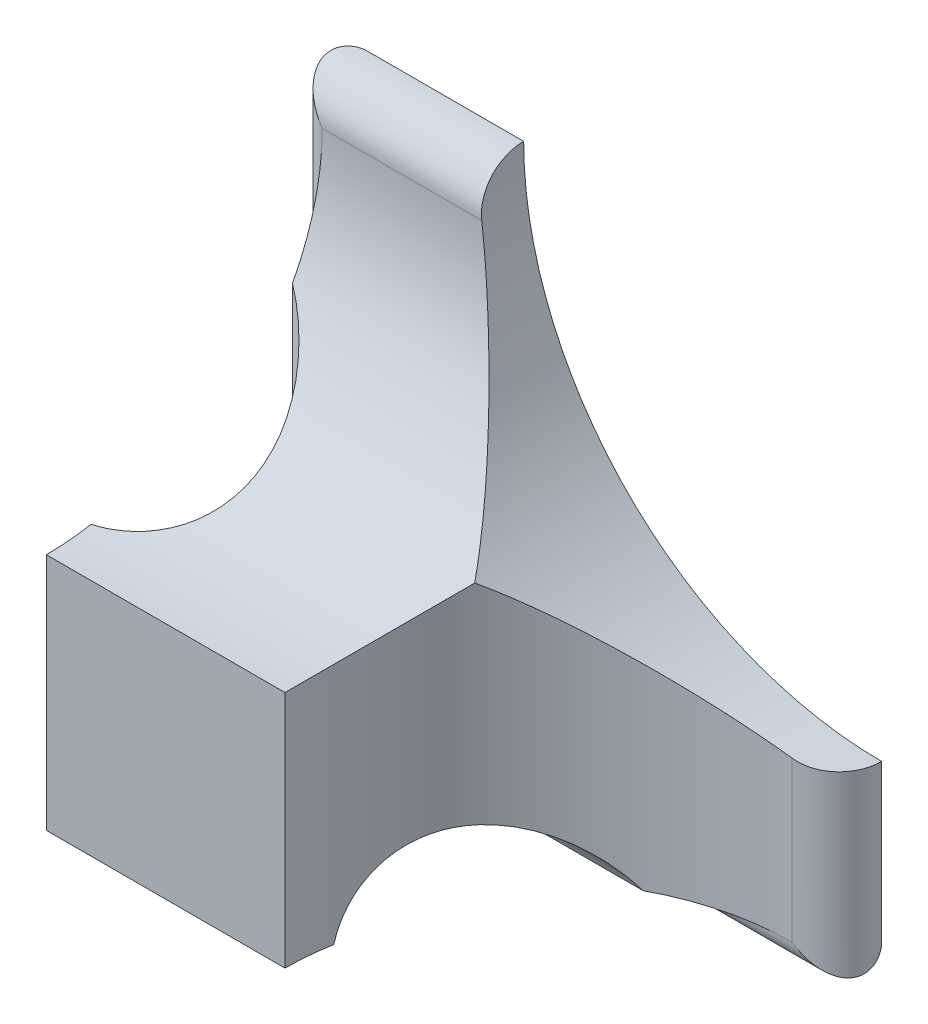
SolidWorks part; units mm, degrees
material "Золото без примесей"
ref_plane "Front" through (0, 0, 0) normal (0, 0, 1) x (1, 0, 0)
ref_plane "Top" through (0, 0, 0) normal (0, 1, 0) x (1, 0, 0)
ref_plane "Right" through (0, 0, 0) normal (1, 0, 0) x (0, 0, -1)
sketch "Эскиз1" plane through (0, 0, 0) normal (0, 0, 1) x (1, 0, 0)
  line L0 (0, 0) -> (18, 0)
  line L1 (18, 0) -> (18, 6)
  line L2 (0, 0) -> (19.7111, 19.7111) construction
  line L4 (9.5147, 9.5147) -> (0, 0)
  line L5 (18, 6) -> (22.8779, 6) construction
  line L6 (9.5147, 9.5147) -> (5.6915, 13.3379) construction
  arc A0 (18, 6) -> (9.5147, 9.5147) centre (18, 18) cw
  dimension "D1" = 45
  dimension "D2" = 6
  dimension "D3" = 18
extrude "Основная форма" add sketch "Эскиз1" along normal blind 10
sketch "Эскиз2" plane through (18, 0, 0) normal (1, 0, 0) x (0, 0, -1)
  line L1 (-10, -1) -> (0, -1)
  line L2 (0, 0.75) -> (0, -1)
  line L5 (-10, 0) -> (0, 0) construction
  line L6 (-10, 0) -> (-10, -1)
  line L8 (-10, 0) -> (-8.5, 0)
  line L10 (-1.5, 0.75) -> (-2.5, 0.75)
  line L11 (0, 0) -> (0, 6) construction
  line L12 (-10.4143, 2.5) -> (-4.9819, 2.5) construction
  arc A3 (-8.5, 0) -> (-2.5, 0.75) centre (-5.3634, -0.7176) cw
  arc A4 (0, 0.75) -> (-1.5, 0.75) centre (-0.75, 0.75) cw
  dimension "D1" = 2.5
  dimension "D2" = 1
  dimension "D3" = 1.5
  dimension "D5" = 1
  dimension "D7" = 1.5
extrude "Вырез фигурный, фронт" cut sketch "Эскиз2" against normal through all
sketch "Эскиз3" plane through (0, 0, 0) normal (0, 1, 0) x (1, 0, 0)
  line L4 (18, 0) -> (18, -10)
  line L6 (18, -10) -> (8, -10)
  line L9 (0, -10) -> (18, -10) construction
  line L10 (0.75, -1.5) -> (18, -1.5) construction
  line L11 (16.5, -10) -> (16.5, -1.5) construction
  arc A4 (8, -10) -> (16.5, -1.5) centre (16.5, -10) cw
  arc A5 (16.5, -1.5) -> (18, 0) centre (16.5, 0) ccw
extrude "Вырез фигурный, бок" cut sketch "Эскиз3" along normal through all
sketch "Эскиз5" plane through (0, 0, 0) normal (0, 0, -1) x (-1, 0, 0)
  line L1 (-8, 4) -> (-4, 4) construction
  line L2 (-18, 0) -> (-18, 6) construction
  line L6 (-9.5147, 9.5147) -> (-0.75, 0.75) construction
  line L7 (-18, 0.75) -> (-0.75, 0.75) construction
  line L8 (-5.1716, 5.1716) -> (-1.5149, 8.8283) construction
  line L9 (-8, 8) -> (-9.5147, 9.5147) construction
  line L10 (-8, 4) -> (-11, 4)
  arc A0 (-5.1716, 5.1716) -> (-8, 4) centre (-8, 8) cw
  point P12 (-18, 3)
  point P15 (0, 0)
  dimension "D2" = 4
  dimension "D1" = 7
  dimension "D3" = 1
extrude "Вырез под финсатор" cut sketch "Эскиз5" against normal blind 3 and the other way through all thin thin type mid plane wall 1.4
mirror "Зеркальное отражение1" about plane through (9.5147, 9.5147, 10) normal (0.7071, -0.7071, 0) of "Вырез под финсатор", "Вырез фигурный, фронт", "Вырез фигурный, бок", "Основная форма"
chamfer "Фаска1" distance 0.5 angle 45 8 edges at (11, 4, 0) (9.5, 4.7, 0) (5.6665, 5.6665, 0) (9.5, 3.3, 0) (4.6766, 4.6766, 0) (4.7, 9.5, 0) (3.3, 9.5, 0) (4, 11, 0)
